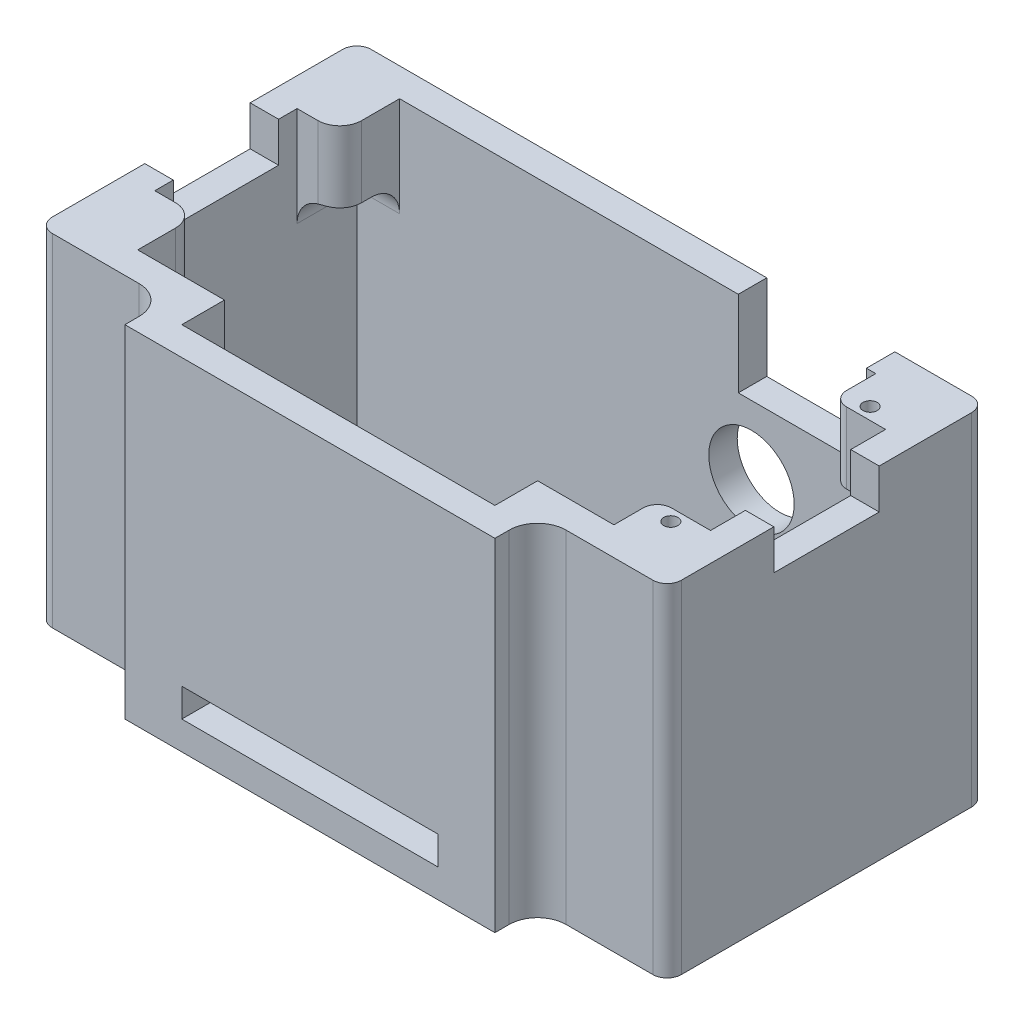
SolidWorks part; units mm, degrees
ref_plane "Front Plane" through (0, 0, 0) normal (0, 0, 1) x (1, 0, 0)
ref_plane "Top Plane" through (0, 0, 0) normal (0, 1, 0) x (1, 0, 0)
ref_plane "Right Plane" through (0, 0, 0) normal (1, 0, 0) x (0, 0, -1)
sketch "Sketch1" plane through (0, 0, 0) normal (0, 1, 0) x (1, 0, 0)
  line L1 (-28.067, -14.224) -> (28.067, -14.224)
  line L2 (-28.067, -14.224) -> (-28.067, 14.224)
  line L3 (-28.067, 14.224) -> (28.067, 14.224)
  line L4 (28.067, -14.224) -> (28.067, 14.224)
  line L5 (-28.067, -14.224) -> (28.067, 14.224) construction
  line L6 (-28.067, 14.224) -> (28.067, -14.224) construction
  point P0 (0, 0)
  dimension "D1" = 56.134
  dimension "D2" = 28.448
extrude "Boss-Extrude1" add sketch "Sketch1" along normal blind 30.48
shell "Shell1" thickness 2.54 removed face at (0, 30.48, 0)
sketch "Sketch2" plane through (0, 0, 0) normal (0, -1, 0) x (1, 0, 0)
  line L0 (0, 0) -> (36.576, 0) construction
  line L1 (28.067, 14.224) -> (28.067, -14.224) construction
  line L2 (23.622, -6.477) -> (12.954, -6.477)
  line L3 (23.622, -6.477) -> (23.622, 6.477)
  line L4 (23.622, 6.477) -> (12.954, 6.477)
  line L5 (12.954, -6.477) -> (12.954, 6.477)
  line L6 (23.622, -6.477) -> (12.954, 6.477) construction
  line L7 (23.622, 6.477) -> (12.954, -6.477) construction
  point P3 (18.288, 0)
  dimension "D1" = 12.954
  dimension "D2" = 10.668
  dimension "D3" = 4.445
extrude "Cut-Extrude1" cut sketch "Sketch2" against normal up to surface (2.54 mm away) up to face at (0, 2.54, 0)
sketch "Sketch3" plane through (0, 30.48, 0) normal (0, 1, 0) x (1, 0, 0)
  line L0 (0, 0) -> (-37.2945, 0) construction
  line L1 (-25.527, 11.684) -> (-25.527, -11.684) construction
  line L17 (-25.527, 11.684) -> (-25.527, 6.35)
  line L19 (-21.717, 11.684) -> (-21.717, 8.3058)
  line L20 (-23.6728, 6.35) -> (-25.527, 6.35)
  line L21 (-21.717, -11.684) -> (-21.717, -8.3058)
  line L22 (-23.6728, -6.35) -> (-25.527, -6.35)
  line L23 (-25.527, -11.684) -> (-25.527, -6.35)
  line L24 (-21.717, -11.684) -> (-25.527, -11.684)
  line L25 (25.527, 11.684) -> (-25.527, 11.684) construction
  line L26 (25.527, 11.684) -> (20.7772, 11.684)
  line L27 (20.7772, 11.684) -> (20.7772, 9.0805)
  line L28 (25.527, 7.8105) -> (25.527, 11.684)
  line L29 (25.527, -11.684) -> (25.527, 11.684) construction
  line L30 (-25.527, 11.684) -> (-21.717, 11.684)
  line L34 (25.527, -11.684) -> (25.527, 11.684) construction
  line L35 (25.527, 7.8105) -> (22.0472, 7.8105)
  line L36 (25.527, -7.8105) -> (25.527, -11.684)
  line L37 (25.527, -11.684) -> (20.7772, -11.684)
  line L38 (20.7772, -11.684) -> (20.7772, -9.0805)
  line L39 (25.527, -7.8105) -> (22.0472, -7.8105)
  arc A6 (-21.717, 8.3058) -> (-23.6728, 6.35) centre (-23.6728, 8.3058) cw
  arc A7 (-21.717, -8.3058) -> (-23.6728, -6.35) centre (-23.6728, -8.3058) ccw
  arc A10 (20.7772, 9.0805) -> (22.0472, 7.8105) centre (22.0472, 9.0805) ccw
  arc A11 (20.7772, -9.0805) -> (22.0472, -7.8105) centre (22.0472, -9.0805) cw
  dimension "D2" = 12.7
  dimension "D3" = 1.9558
  dimension "D5" = 1.27
  dimension "D1" = 3.81
  dimension "D4" = 15.621
  dimension "D6" = 45.72
extrude "Boss-Extrude2" add sketch "Sketch3" against normal blind 6.35
sketch "Sketch4" plane through (-28.067, 0, 0) normal (-1, 0, 0) x (0, 0, 1)
  line L0 (-14.224, 30.48) -> (14.224, 30.48) construction
  line L1 (-14.224, 30.48) -> (14.224, 30.48) construction
  line L3 (-4.699, 26.924) -> (4.699, 26.924)
  line L4 (-4.699, 26.924) -> (-4.699, 34.036)
  line L5 (-4.699, 34.036) -> (4.699, 34.036)
  line L6 (4.699, 26.924) -> (4.699, 34.036)
  line L7 (-4.699, 26.924) -> (4.699, 34.036) construction
  line L8 (-4.699, 34.036) -> (4.699, 26.924) construction
  point P2 (0, 30.48)
  dimension "D1" = 9.398
  dimension "D2" = 3.556
extrude "Cut-Extrude2" cut sketch "Sketch4" against normal up to surface (56.134 mm away) contours L4 L3 L6 L5 up to face at (28.067, 15.24, 0)
sketch "Sketch6" plane through (0, 30.48, 0) normal (0, 1, 0) x (1, 0, 0)
  line L0 (-28.067, -14.224) -> (28.067, -14.224) construction
  line L5 (-16.51, -14.224) -> (16.51, -14.224)
  line L6 (-16.51, -14.224) -> (-16.51, -18.034)
  line L7 (-16.51, -18.034) -> (16.51, -18.034)
  line L8 (16.51, -18.034) -> (16.51, -14.224)
  line L9 (0, 0) -> (0, -27.7045) construction
  point P9 (0, -14.224)
  dimension "D1" = 3.81
  dimension "D2" = 33.02
extrude "Boss-Extrude3" add sketch "Sketch6" against normal up to surface (30.48 mm away) up to face at (18.288, 0, 0)
sketch "Sketch7" plane through (0, 30.48, 0) normal (0, 1, 0) x (1, 0, 0)
  line L0 (-16.51, -18.034) -> (16.51, -18.034) construction
  line L1 (-21.717, -11.684) -> (20.7772, -11.684) construction
  line L2 (-16.51, -18.034) -> (16.51, -18.034)
  line L3 (-13.97, -11.684) -> (13.97, -11.684)
  line L4 (-13.97, -11.684) -> (-13.97, -15.494)
  line L5 (-13.97, -15.494) -> (13.97, -15.494)
  line L6 (13.97, -15.494) -> (13.97, -11.684)
  line L7 (-16.51, -14.224) -> (-16.51, -18.034) construction
  line L8 (16.51, -18.034) -> (16.51, -14.224) construction
  line M29 (20.7772, -11.684) -> (-21.717, -11.684)
  dimension "D1" = 2.54
  dimension "D2" = 2.54
  dimension "D3" = 2.54
extrude "Cut-Extrude3" cut sketch "Sketch7" against normal offset from surface (27.94 mm away) 2.54 contours L5 L6 L4 M29 region at (0, 30.48, 13.589) up to face at (18.288, 0, 0)
fillet "Fillet1" radius 2.54 2 edges at (16.51, 15.24, 14.224) (-16.51, 15.24, 14.224)
fillet "Fillet2" radius 1.27 4 edges at (28.067, 15.24, 14.224) (28.067, 15.24, -14.224) (-28.067, 15.24, -14.224) (-28.067, 15.24, 14.224)
sketch "Sketch8" plane through (0, 0, -14.224) normal (0, 0, -1) x (-1, 0, 0)
  circle A0 centre (-9.6841, 16.7451) radius 3.81
  dimension "D1" = 7.62
extrude "Cut-Extrude4" cut sketch "Sketch8" against normal up to surface (2.54 mm away) up to face at (-0.2349, 20.32, -11.684)
fillet "Fillet3" radius 2.54 8 edges at (-25.527, 24.13, 9.017) (-23.622, 24.13, 11.684) (23.1521, 24.13, 11.684) (25.527, 24.13, 9.7472) (-23.622, 24.13, -11.684) (-25.527, 24.13, -9.017) (23.1521, 24.13, -11.684) (25.527, 24.13, -9.7473)
sketch "Sketch9" plane through (0, 0, -14.224) normal (0, 0, -1) x (-1, 0, 0)
  line L0 (-26.797, 30.48) -> (26.797, 30.48) construction
  line L1 (-19.939, 30.48) -> (-8.509, 30.48)
  line L2 (-19.939, 30.48) -> (-19.939, 22.86)
  line L3 (-19.939, 22.86) -> (-8.509, 22.86)
  line L4 (-8.509, 30.48) -> (-8.509, 22.86)
  line L5 (-28.067, 0) -> (-28.067, 30.48) construction
  dimension "D1" = 7.62
  dimension "D2" = 11.43
  dimension "D3" = 8.128
extrude "Cut-Extrude5" cut sketch "Sketch9" against normal up to surface (2.54 mm away) up to face at (13.4941, 16.7451, -11.684)
sketch "Sketch10" plane through (0, 0, -14.224) normal (0, 0, -1) x (-1, 0, 0)
  line L0 (-26.797, 0) -> (26.797, 0) construction
  line L1 (-11.43, 2.54) -> (11.43, 2.54)
  line L2 (-11.43, 2.54) -> (-11.43, 5.08)
  line L3 (-11.43, 5.08) -> (11.43, 5.08)
  line L4 (11.43, 2.54) -> (11.43, 5.08)
  point P4 (0, 2.54)
  dimension "D1" = 2.54
  dimension "D2" = 2.54
  dimension "D3" = 22.86
extrude "Cut-Extrude6" cut sketch "Sketch10" against normal up to surface (32.258 mm away) up to face at (0, 15.24, 18.034)
sketch "Sketch11" plane through (0, 30.48, 0) normal (0, 1, 0) x (1, 0, 0)
  line L1 (23.0632, 8.89) -> (23.0632, -8.89) construction
  line L2 (20.7772, 11.684) -> (20.7772, 9.0805) construction
  circle A0 centre (23.0632, 8.89) radius 0.635
  circle A1 centre (23.0632, -8.89) radius 0.635
  point P7 (23.0632, 0)
  point P8 (23.0632, 10.0727)
  dimension "D2" = 1.27
  dimension "D1" = 17.78
  dimension "D3" = 2.286
extrude "Cut-Extrude7" cut sketch "Sketch11" against normal blind 11.938
